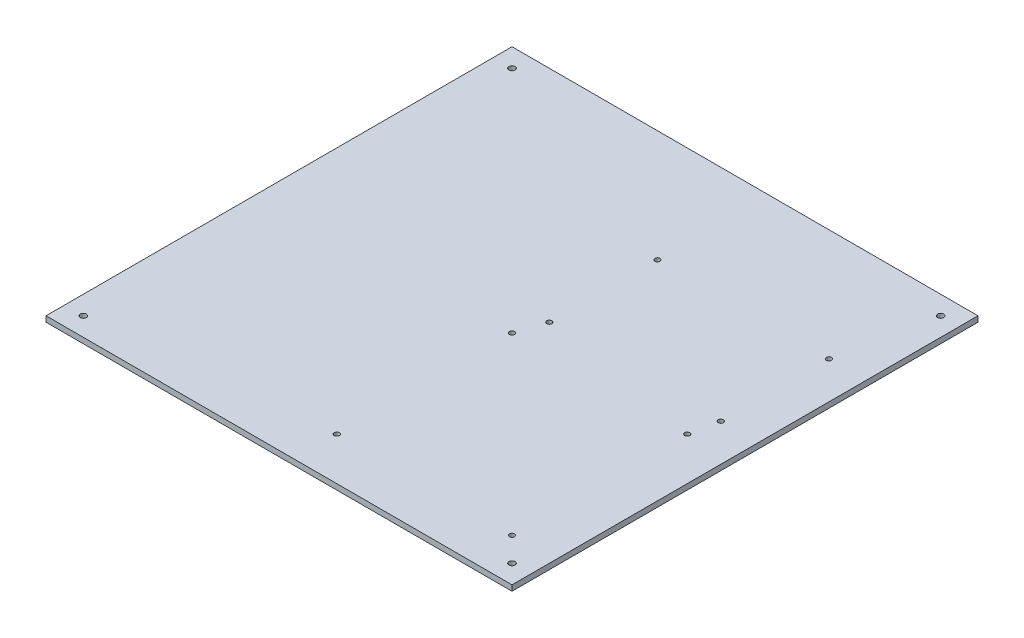
SolidWorks part; units mm, degrees
ref_plane "Front Plane" through (0, 0, 0) normal (0, 0, 1) x (1, 0, 0)
ref_plane "Top Plane" through (0, 0, 0) normal (0, 1, 0) x (1, 0, 0)
ref_plane "Right Plane" through (0, 0, 0) normal (1, 0, 0) x (0, 0, -1)
sketch "Sketch1" plane through (0, 0, 0) normal (0, 1, 0) x (1, 0, 0)
  line L0 (0, 0) -> (0, -250) construction
  line L1 (-125, 0) -> (125, 0)
  line L2 (-125, 0) -> (-125, -250)
  line L3 (-125, -250) -> (125, -250)
  line L4 (125, 0) -> (125, -250)
  line L5 (0, -1.65) -> (0, 1.65) construction
  line L6 (-125, -125) -> (125, -125) construction
  line L7 (55, -130) -> (55, -230) construction
  line L8 (-105, -161.34) -> (-31.34, -161.34) construction
  line L9 (-105, -15) -> (-31.34, -15) construction
  line L10 (-105, -15) -> (-105, -88.66) construction
  line L11 (-105, -88.66) -> (-31.34, -88.66) construction
  line L12 (-31.34, -15) -> (-31.34, -88.66) construction
  line L13 (-105, -161.34) -> (-105, -235) construction
  line L14 (-105, -235) -> (-31.34, -235) construction
  line L15 (-31.34, -161.34) -> (-31.34, -235) construction
  line L16 (-105, -88.66) -> (-105, -161.34) construction
  line L17 (5, -130) -> (105, -130) construction
  line L18 (5, -130) -> (5, -230) construction
  line L19 (5, -230) -> (105, -230) construction
  line L20 (105, -130) -> (105, -230) construction
  line L21 (5, -180) -> (105, -180) construction
  line L22 (-60.805, -122.8687) -> (-38.005, -122.8687) construction
  line L23 (9, -43) -> (109, -43) construction
  line L24 (9, -43) -> (9, -122) construction
  line L25 (9, -122) -> (109, -122) construction
  line L26 (109, -43) -> (109, -122) construction
  line L27 (-102.037, -122.1462) -> (-79.237, -122.1462) construction
  line L28 (-102.037, -122.1462) -> (-102.037, -145.0462) construction
  line L29 (-102.037, -145.0462) -> (-79.237, -145.0462) construction
  line L30 (-79.237, -122.1462) -> (-79.237, -145.0462) construction
  line L35 (-60.805, -122.8687) -> (-60.805, -145.7687) construction
  line L36 (-60.805, -145.7687) -> (-38.005, -145.7687) construction
  line L37 (-38.005, -122.8687) -> (-38.005, -145.7687) construction
  circle A3 centre (-115, -240) radius 1.65
  circle A4 centre (115, -240) radius 1.65
  circle A5 centre (-115, -10) radius 1.65
  circle A6 centre (115, -10) radius 1.65
  circle A7 centre (13, -60) radius 1.375
  circle A8 centre (13, -118) radius 1.375
  circle A9 centre (105, -118) radius 1.375
  circle A10 centre (105, -60) radius 1.375
  circle A11 centre (8, -133) radius 1.375
  circle A12 centre (102, -133) radius 1.375
  circle A13 centre (102, -227) radius 1.375
  circle A14 centre (8, -227) radius 1.375
  dimension "D1" = 3.3
  dimension "D2" = 10
  dimension "D12" = 2.75
  dimension "D20" = 2.75
  dimension "D3" = 10
  dimension "D4" = 250
  dimension "D5" = 250
  dimension "D6" = 73.66
  dimension "D7" = 15
  dimension "D8" = 20
  dimension "D9" = 58
  dimension "D10" = 92
  dimension "D11" = 58
  dimension "D13" = 20
  dimension "D14" = 60
  dimension "D15" = 100
  dimension "D16" = 100
  dimension "D17" = 20
  dimension "D18" = 20
  dimension "D19" = 3
  dimension "D21" = 3
  dimension "D22" = 17
  dimension "D23" = 79
  dimension "D24" = 100
  dimension "D25" = 4
  dimension "D26" = 22.9
  dimension "D27" = 22.8
extrude "Boss-Extrude1" add sketch "Sketch1" along normal blind 3
equation "\"cf_tube_outer_diameter\"= 25mm"
equation "\"cf_tube_inner_diameter\"= 21mm"
equation "\"mid_plate_mid_to_top\"= 100mm"
equation "\"mid_plate_mid_to_bottom\"= 30mm"
equation "\"mid_plate_horizontal_spacing\"= 250mm"
equation "\"cf_plate_thickness\"= 3mm"
equation "\"mid_tube_length\"= 500mm"
equation "\"mid_plate_bottom_width\"= 180mm"
equation "\"mid_support_plate_distance\"= 250mm"
equation "\"nut_strip_2_hole_distance\"= 7mm"
equation "\"nut_strip_hole_diameter\"= 2.5mm"
equation "\"nut_strip_hole_to_edge_distance\"= 2.5mm"
